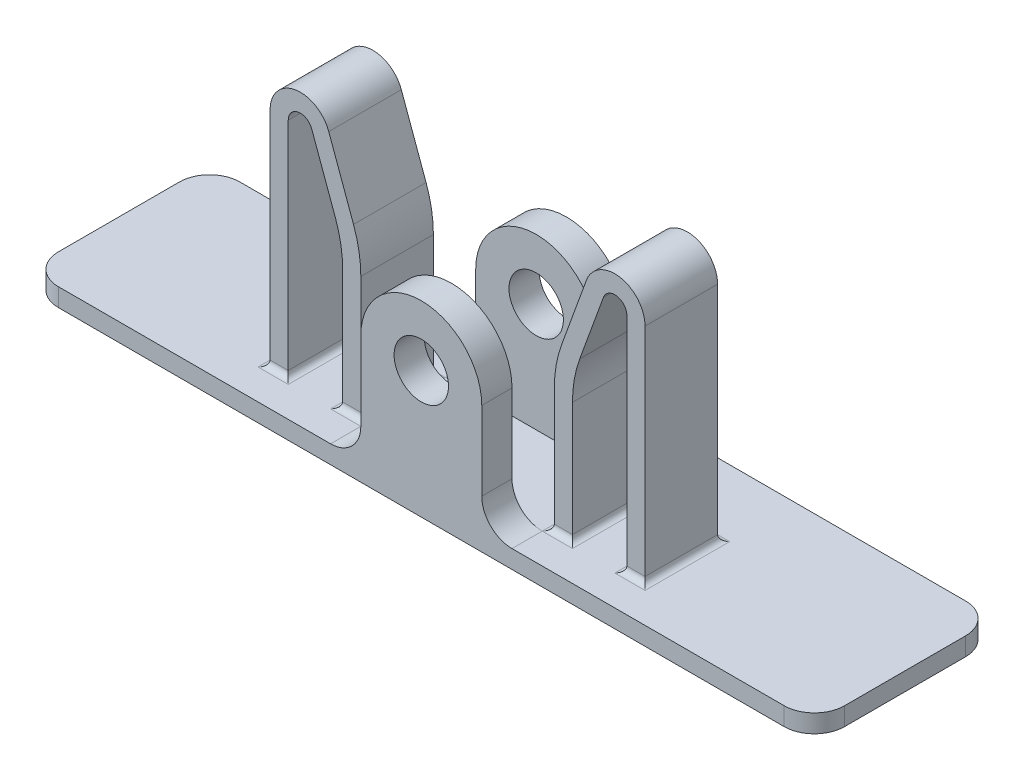
SolidWorks part; units mm, degrees
ref_plane "Front Plane" through (0, 0, 0) normal (0, 0, 1) x (1, 0, 0)
ref_plane "Top Plane" through (0, 0, 0) normal (0, 1, 0) x (1, 0, 0)
ref_plane "Right Plane" through (0, 0, 0) normal (1, 0, 0) x (0, 0, -1)
sketch "Sketch1" plane through (0, 0, 0) normal (0, 1, 0) x (1, 0, 0)
  line L1 (65, -12) -> (-65, -12)
  line L2 (65, -12) -> (65, 12)
  line L3 (65, 12) -> (-65, 12)
  line L4 (-65, -12) -> (-65, 12)
  line L5 (65, -12) -> (-65, 12) construction
  line L6 (65, 12) -> (-65, -12) construction
  point P0 (0, 0)
  dimension "D1" = 130
  dimension "D2" = 24
extrude "Boss-Extrude1" add sketch "Sketch1" along normal blind 3
sketch "Sketch2" plane through (0, 0, 12) normal (0, 0, 1) x (1, 0, 0)
  line L0 (-65, 3) -> (65, 3) construction
  line L2 (-10, 3) -> (10, 3)
  line L3 (-10, 3) -> (-10, 21)
  line L4 (-10, 21) -> (10, 21)
  line L5 (10, 3) -> (10, 21)
  circle A0 centre (0, 21) radius 10
  dimension "D1" = 20
  dimension "D2" = 18
extrude "Boss-Extrude2" add sketch "Sketch2" against normal blind 5 contours A0 | L3 L2 L5 L4
mirror "Mirror1" about plane through (0, 0, 0) normal (0, 0, 1) of "Boss-Extrude2"
hole_wizard "M8 Clearance Hole1" positions "Sketch3" profile "Sketch4" hole size "M8" standard "ANSI Metric" end condition through all
sketch "Sketch3" plane through (0, 0, 12) normal (0, 0, 1) x (1, 0, 0)
  point P0 (0, 21)
sketch "Sketch4" plane through (0, 21, 12) normal (1, 0, 0) x (0, -1, 0)
  line L0 (0, 0) -> (0, 24)
  line L1 (0, 24) -> (4.5, 24)
  line L2 (4.5, 24) -> (4.5, 0)
  line L5 (4.5, 0) -> (0, 0)
  line L11 (0, -6.35) -> (0, 107.95) construction
  dimension "Thru Hole Dia." = 9
  dimension "Thru Hole Depth" = 24
sketch "Sketch6" plane through (0, 0, -12) normal (0, 0, -1) x (-1, 0, 0)
  line L1 (-65, 0) -> (65, 0)
  line L2 (-65, 0) -> (-65, 3)
  line L3 (-65, 3) -> (65, 3)
  line L4 (65, 0) -> (65, 3)
extrude "Boss-Extrude3" add sketch "Sketch6" along normal blind 6
sketch "Sketch7" plane through (0, 0, 0) normal (0, 0, 1) x (1, 0, 0)
  line L0 (16, 0) -> (16, 27)
  line L2 (16, 27) -> (21.3015, 41.5659)
  line L3 (31, 39.8558) -> (31, 0)
  line L4 (31, 0) -> (16, 0)
  line L5 (-0.0244, 20.8063) -> (12.8467, 56.1693) construction
  line L6 (0, 0) -> (0, 33.9292) construction
  line L7 (16, 27) -> (31, 27) construction
  line L8 (-65, 0) -> (65, 0) construction
  arc A0 (21.3015, 41.5659) -> (31, 39.8558) centre (26, 39.8558) cw
  dimension "D6" = 5
  dimension "D1" = 20
  dimension "D2" = 15
  dimension "D3" = 70
  dimension "D4" = 16
  dimension "D5" = 27
extrude "Extrude-Thin1" add sketch "Sketch7" along normal mid plane 12 thin thin type one direction reverse wall 3
mirror "Mirror2" about plane through (0, 0, 0) normal (1, 0, 0) of "Extrude-Thin1"
fillet "Fillet1" radius 20 4 edges at (16, 27, 0) (-16, 27, 0) (19, 26.471, 0) (-19, 26.471, 0)
fillet "Fillet2" radius 5 4 edges at (-65, 1.5, -18) (65, 1.5, -18) (65, 1.5, 12) (-65, 1.5, 12)
fillet "Fillet3" radius 5 4 edges at (10, 3, -9.5) (-10, 3, -9.5) (-10, 3, 9.5) (10, 3, 9.5)
fillet "Fillet4" radius 1 16 edges at (-29.5, 3, 6) (-17.5, 3, 6) (-16, 3, 0) (-31, 3, 0) (-19, 3, 0) (-28, 3, 0) (-17.5, 3, -6) (-29.5, 3, -6) (29.5, 3, -6) (17.5, 3, -6) (19, 3, 0) (16, 3, 0) (17.5, 3, 6) (29.5, 3, 6) (28, 3, 0) (31, 3, 0)
